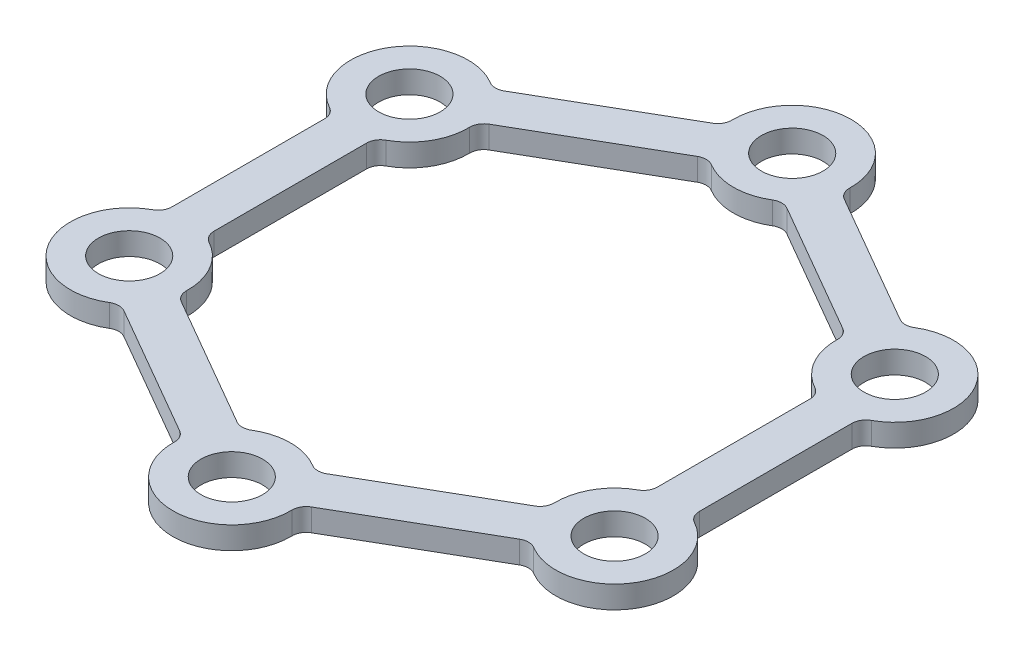
SolidWorks part; units mm, degrees
ref_plane "Front Plane" through (0, 0, 0) normal (0, 0, 1) x (1, 0, 0)
ref_plane "Top Plane" through (0, 0, 0) normal (0, 1, 0) x (1, 0, 0)
ref_plane "Right Plane" through (0, 0, 0) normal (1, 0, 0) x (0, 0, -1)
sketch "Sketch1" plane through (0, 0, 0) normal (0, 1, 0) x (1, 0, 0)
  line L1 (0, 10) -> (-8.6603, 5)
  line L2 (-8.6603, 5) -> (-8.6603, -5)
  line L3 (-8.6603, -5) -> (0, -10)
  line L4 (0, -10) -> (8.6603, -5)
  line L5 (8.6603, -5) -> (8.6603, 5)
  line L6 (8.6603, 5) -> (0, 10)
  circle A0 centre (0, 0) radius 10 construction
  dimension "D1" = 20
sketch "Sketch2" plane through (0, 0, 0) normal (0, 1, 0) x (1, 0, 0)
  line L0 (1.3237, 8.3697) -> (6.5865, 5.3312)
  line L1 (8.6603, 5) -> (0, 10) construction
  line L2 (8.6603, 5) -> (0, 10) construction
  line L3 (2.0737, 9.6688) -> (7.3365, 6.6303)
  circle A0 centre (0, 10) radius 1.1
  circle A1 centre (0, 10) radius 2.1
  circle A2 centre (8.6603, 5) radius 1.1 construction
  circle A3 centre (8.6603, 5) radius 2.1 construction
  arc A4 (6.5865, 5.3312) -> (7.3365, 6.6303) centre (8.6603, 5) cw
  dimension "D1" = 2.2
  dimension "D4" = 1.5
  dimension "D2" = 1
  dimension "D3" = 2
extrude "Boss-Extrude1" add sketch "Sketch2" along normal blind 0.8 contours A1 A0 | L0 A4 L3 A1 region at (4.3301, 0, -7.5) region at (-1.8424, 0, -10.8773)
sketch "Sketch3" plane through (0, 0.8, 0) normal (0, 1, 0) x (1, 0, 0)
  point P0 (0, 0)
ref_axis "Axis1" through (0, 0.8, 0) along (0, -1, 0)
pattern_circular "CirPattern1" count 6 over 360 about axis through (0, 0.8, 0) along (0, -1, 0) of "Boss-Extrude1"
fillet "Fillet1" radius 0.5 24 edges at (1.3237, 0.4, -8.3697) (-1.3237, 0.4, -8.3697) (-6.5865, 0.4, -5.3312) (-7.9103, 0.4, -3.0385) (-7.9103, 0.4, 3.0385) (-6.5865, 0.4, 5.3312) (-1.3237, 0.4, 8.3697) (1.3237, 0.4, 8.3697) (6.5865, 0.4, 5.3312) (7.9103, 0.4, 3.0385) (7.9103, 0.4, -3.0385) (6.5865, 0.4, -5.3312) (9.4103, 0.4, -3.0385) (9.4103, 0.4, 3.0385) (7.3365, 0.4, 6.6303) (2.0737, 0.4, 9.6688) (-2.0737, 0.4, 9.6688) (-9.4103, 0.4, 3.0385) (-9.4103, 0.4, -3.0385) (-7.3365, 0.4, -6.6303) (-2.0737, 0.4, -9.6688) (2.0737, 0.4, -9.6688) (7.3365, 0.4, -6.6303) (-7.3365, 0.4, 6.6303)
